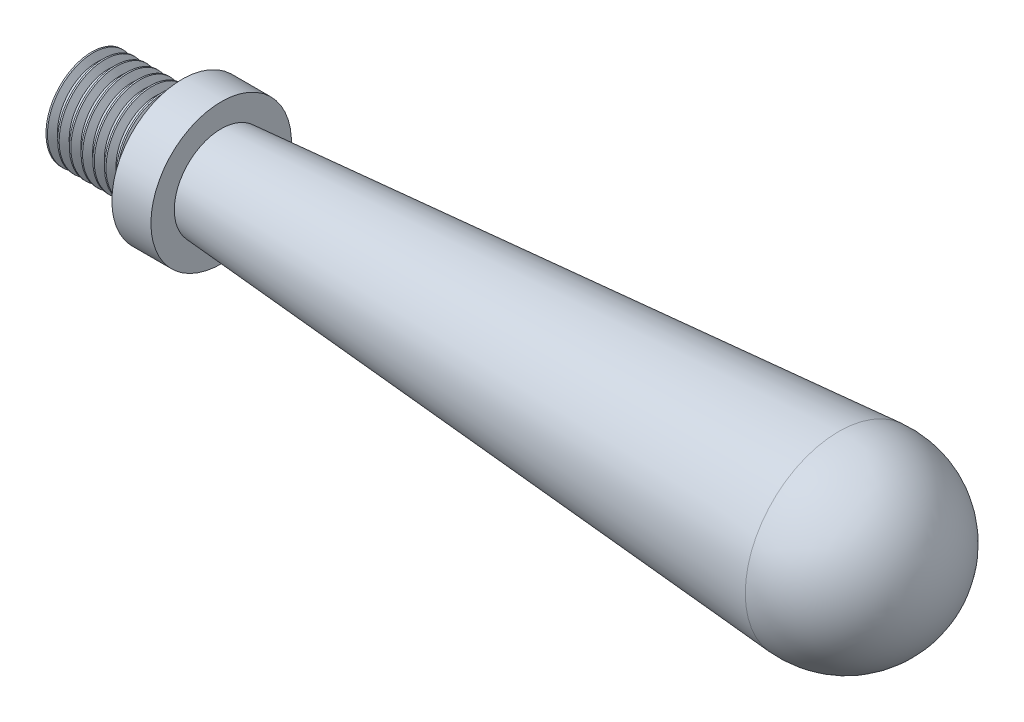
SolidWorks part; units mm, degrees
ref_plane "Front Plane" through (0, 0, 0) normal (0, 0, 1) x (1, 0, 0)
ref_plane "Top Plane" through (0, 0, 0) normal (0, 1, 0) x (1, 0, 0)
ref_plane "Right Plane" through (0, 0, 0) normal (1, 0, 0) x (0, 0, -1)
sketch "Sketch1" plane through (0, 0, 0) normal (0, 0, 1) x (1, 0, 0)
  line L0 (0, 0) -> (97, 0) construction
  line L1 (0, 0) -> (0, 6)
  line L2 (0, 6) -> (12, 6)
  line L3 (12, 6) -> (12, 9)
  line L4 (12, 9) -> (17, 9)
  line L5 (96.0975, 11.966) -> (17, 6)
  line L6 (17, 9) -> (17, 6)
  line L7 (97, 0) -> (109, 0) construction
  line L8 (0, 0) -> (109, 0)
  arc A0 (109, 0) -> (96.0975, 11.966) centre (97, 0) ccw
  dimension "D5" = 24
  dimension "D1" = 97
  dimension "D2" = 12
  dimension "D3" = 12
  dimension "D4" = 18
  dimension "D6" = 12
  dimension "D7" = 5
revolve "Revolve1" add sketch "Sketch1" angle 360 about L8
thread "Thread1" pitch 1.5 method cut profile "Thread Profile1" start angle 0, offset 3, length 0, pitch 1.5, diameter 12
ref_plane "Plane1" through (-3, 0, -6) normal (0, -1, 0) x (0, 0, -1)
sketch "Thread Profile1" plane through (-3, 0, -6) normal (0, -1, 0) x (0, 0, -1)
  line L0 (0, 0) -> (0, 1.5) construction
  line L11 (0, 0) -> (0, 1.3125)
  line L12 (0, 1.3125) -> (-0.8119, 0.8437)
  line L13 (-0.8119, 0.8437) -> (-0.8119, 0.4687)
  line L15 (-0.8119, 0.4687) -> (0, 0)
  line L17 (-0.8119, 0.6562) -> (0, 0.6562) construction
  point P2 (0, 0)
  dimension "Pitch" = 1.5
  dimension "Profile_Angle" = 60
  dimension "Profile_Land" = 0.375
  dimension "Profile_Height" = 0.8119
